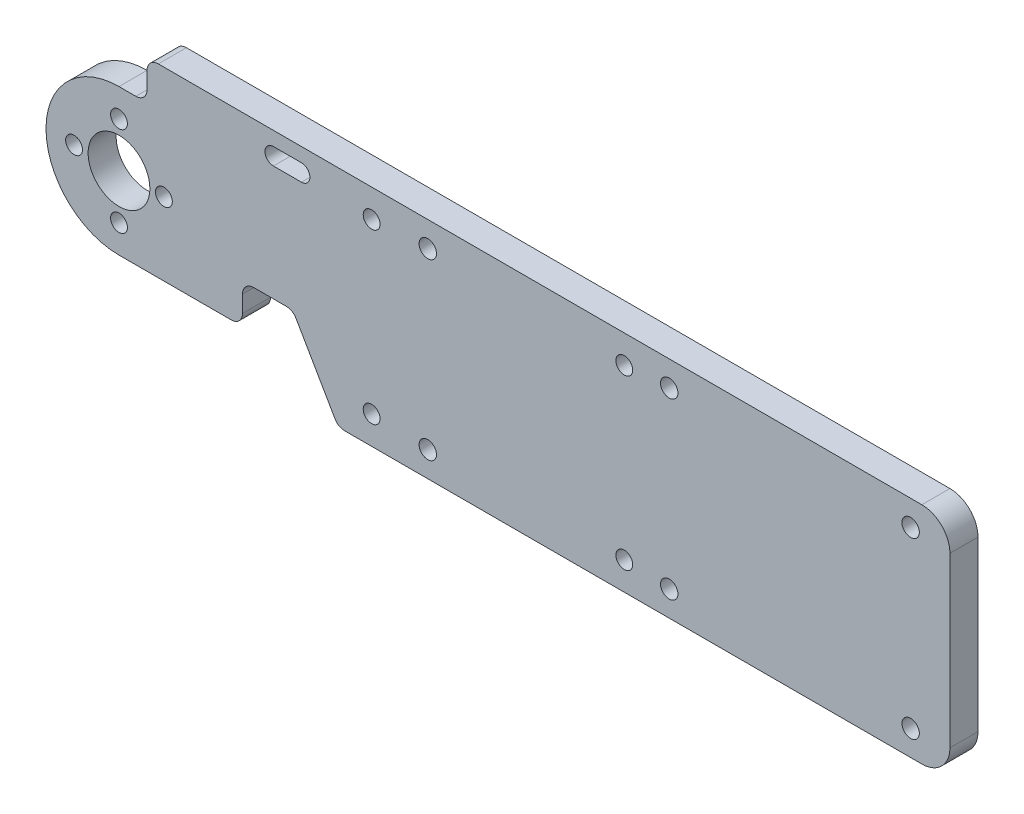
SolidWorks part; units mm, degrees
material "Acrylic (Medium-high impact)"
ref_plane "Front Plane" through (0, 0, 0) normal (0, 0, 1) x (1, 0, 0)
ref_plane "Top Plane" through (0, 0, 0) normal (0, 1, 0) x (1, 0, 0)
ref_plane "Right Plane" through (0, 0, 0) normal (1, 0, 0) x (0, 0, -1)
sketch "Sketch2" plane through (0, 0, 0) normal (0, 0, 1) x (1, 0, 0)
  line L0 (0, 20) -> (0, -20)
  line L1 (0, 20) -> (148, 20)
  line L2 (0, -20) -> (148, -20)
  line L3 (148, 20) -> (148, -20)
  line L4 (0, 0) -> (-17, 0)
  line L5 (0, -13) -> (35, -13)
  line L6 (35, -13) -> (35, -20)
  line L7 (5, 13) -> (22, -6)
  line L8 (0, 13) -> (5, 13)
  line L9 (0, 13) -> (0, 20)
  line L10 (0, 20) -> (5, 20)
  line L11 (5, 13) -> (5, 20)
  line L12 (35, -13) -> (39.0415, -20)
  line L13 (22, -13) -> (35, -13)
  line L14 (22, -13) -> (22, -6)
  line L15 (22, -6) -> (35, -6)
  line L16 (35, -13) -> (35, -6)
  line L17 (35, -13) -> (30.9585, -6)
  circle A1 centre (0, 0) radius 5.5
  circle A2 centre (0, 0) radius 13
  dimension "D1" = 148
  dimension "D3" = 11
  dimension "D6" = 26
  dimension "D2" = 165
  dimension "D4" = 40
  dimension "D5" = 20
  dimension "D7" = 35
  dimension "D8" = 22
  dimension "D9" = 7
  dimension "D10" = 5
  dimension "D11" = 60
  dimension "D12" = 60
extrude "Boss-Extrude1" add sketch "Sketch2" along normal mid plane 5 contours A2 L2 L3 L1 | A1 L4 A2 L0 | A1 L0 A2 L4 | A2 L5 | A2 L8 | L7 A2 L0 A1 | L7 A2 | L17 L16 L15 region at (6.1639, -0.1248, 0) region at (4.3258, 12.5044, 0) region at (-6.2113, 6.2113, 0) region at (83.3624, 1.0992, 0) region at (9.4178, 8.4264, 0) region at (-6.2113, -6.2113, 0) region at (15.1507, -7.4075, 0) region at (33.6528, -8.3333, 0)
fillet "Fillet1" radius 5 2 edges at (148, -20, 0) (148, 20, 0)
sketch "Sketch3" plane through (0, 0, -2.5) normal (0, 0, -1) x (-1, 0, 0)
  line L0 (-119.5, 20) -> (-119.5, -20)
  line L1 (-119.5, 0) -> (-98, 0)
  line L2 (-98, 0) -> (-98, 15.5)
  line L9 (-119.5, 0) -> (-75.2347, 0)
  line L12 (0, 0) -> (0, 12)
  line L13 (0, 0) -> (-83, 0)
  line L14 (-32.5, 16) -> (-27.5, 16) construction
  line L17 (-32.5, 17.5) -> (-27.5, 17.5)
  line L18 (-32.5, 14.5) -> (-27.5, 14.5)
  line L19 (0, 0) -> (18.4819, 0)
  line L24 (-22, -6) -> (-22, -13)
  line L25 (-148, 15) -> (-148, -15)
  line L27 (-148, 15) -> (-148, -15)
  line L29 (-143, -20) -> (-39.0415, -20)
  line L31 (-143, -20) -> (-39.0415, -20)
  line L33 (-5, 20) -> (-143, 20)
  line L35 (-5, 20) -> (-143, 20)
  line L36 (-39.0415, -20) -> (-30.9585, -6)
  line L38 (-22, -13) -> (0, -13)
  line L39 (-22, -13) -> (0, -13)
  line L40 (0, 13) -> (-5, 13)
  line L41 (0, 13) -> (-5, 13)
  line L42 (-5, 13) -> (-5, 20)
  line L43 (-5, 13) -> (-5, 20)
  line L44 (-30.9585, -6) -> (-22, -6)
  line L45 (-30.9585, -6) -> (-22, -6)
  line L46 (-22, -6) -> (-22, -13)
  line L49 (-39.0415, -20) -> (-30.9585, -6)
  circle A0 centre (0, 0) radius 12
  circle A1 centre (-98, 15.5) radius 1.55
  circle A2 centre (-98, -15.5) radius 1.55
  circle A3 centre (-55, -15.5) radius 1.55
  arc A4 (0, -13) -> (0, 13) centre (0, 0) ccw
  circle A5 centre (-55, 15.5) radius 1.55
  circle A9 centre (-141, -15.5) radius 1.55
  circle A10 centre (-141, 15.5) radius 1.55
  circle A12 centre (-90, -15) radius 1.5
  circle A13 centre (-45, -15) radius 1.5
  arc A21 (-32.5, 17.5) -> (-32.5, 14.5) centre (-32.5, 16) ccw
  arc A22 (-27.5, 14.5) -> (-27.5, 17.5) centre (-27.5, 16) ccw
  circle A24 centre (-90, 15) radius 1.5
  circle A26 centre (-45, 15) radius 1.5
  circle A27 centre (0, 0) radius 8
  circle A28 centre (0, -8) radius 1.5
  circle A29 centre (-8, 0) radius 1.5
  circle A30 centre (0, 8) radius 1.5
  circle A31 centre (8, 0) radius 1.5
  arc A33 (-148, -15) -> (-143, -20) centre (-143, -15) ccw
  arc A34 (-148, -15) -> (-143, -20) centre (-143, -15) ccw
  arc A35 (-143, 20) -> (-148, 15) centre (-143, 15) ccw
  arc A36 (-143, 20) -> (-148, 15) centre (-143, 15) ccw
  arc A42 (0, -13) -> (0, 13) centre (0, 0) ccw
  point P35 (-30, 16)
  point P48 (12, 0)
  point P53 (-12, 0)
  point P54 (-7.6279, -12)
  dimension "D6" = 3.1
  dimension "D10" = 15
  dimension "D11" = 16
  dimension "D13" = 45
  dimension "D17" = 3
  dimension "D18" = 4
  dimension "D12" = 3
  dimension "D19" = 16
  dimension "D22" = 3
  dimension "D3" = 21.5
  dimension "D4" = 15.5
  dimension "D5" = 98
  dimension "D8" = 15
  dimension "D9" = 30
  dimension "D14" = 5
  dimension "D15" = 3
  dimension "D16" = 16
  dimension "D1" = 0
extrude "Cut-Extrude1" cut sketch "Sketch3" against normal through all contours L18 A22 L17 A21 | A5 | A5 | A12 | A2 | A1 | A10 | A9 | A27 A28 | A27 A28 | L19 A31 A27 | A27 A31 L19 | L19 A31 A27 | A27 A31 L19 | A27 A29 L13 | L13 A29 A27 | A27 A29 L13 | L13 A29 A27 | A27 A30 L12 | L12 A30 A27 | A27 A30 L12 | L12 A30 A27 | A3 | A24 | A26 | A13 region at (99.065, 16.565, -2.5) region at (8.6106, 0.6553, -2.5) region at (8.6106, -0.6553, -2.5) region at (-8.6106, -0.6553, -2.5) region at (-8.6106, 0.6553, -2.5) region at (7.3387, 0.6164, -2.5) region at (7.3387, -0.6164, -2.5) region at (-0.6553, 8.6106, -2.5) region at (0.6553, 8.6106, -2.5) region at (-7.3387, -0.6164, -2.5) region at (-7.3387, 0.6164, -2.5) region at (0.6164, 7.3387, -2.5) region at (0, -7.3387, -2.5) region at (0, -8.6106, -2.5) region at (-0.6164, 7.3387, -2.5) region at (30, 16, -2.5) region at (98, -15.5, -2.5) region at (55, -15.5, -2.5) region at (55, 15.5, -2.5) region at (141, -15.5, -2.5) region at (141, 15.5, -2.5) region at (90, -15, -2.5) region at (45, -15, -2.5) region at (90, 15, -2.5) region at (45, 15, -2.5)
fillet "Fillet2" radius 2 6 edges at (5, 20, 0) (5, 13, 0) (22, -13, 0) (22, -6, 0) (39.0415, -20, 0) (30.9585, -6, 0)
